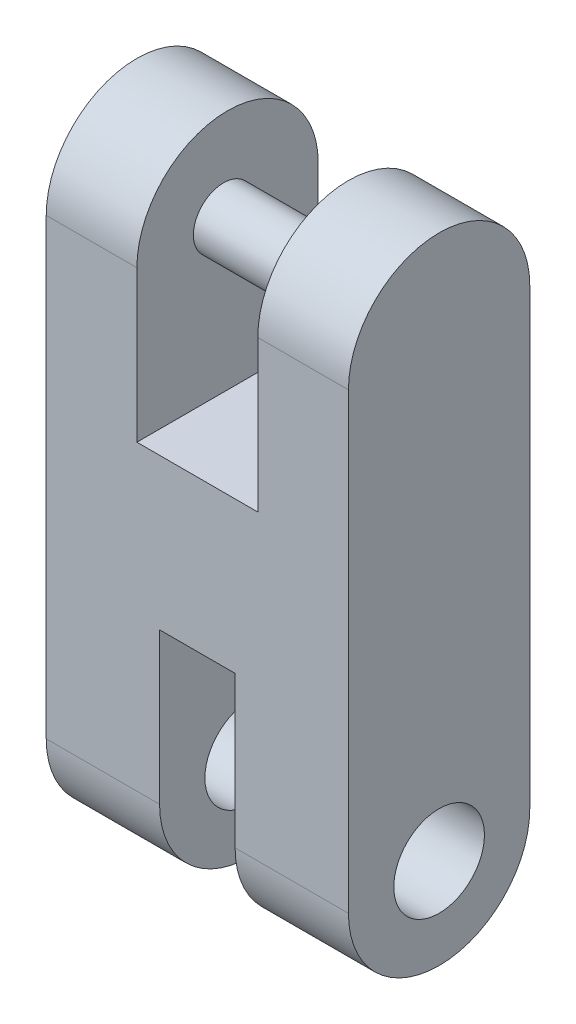
SolidWorks part; units mm, degrees
ref_plane "Alzado" through (0, 0, 0) normal (0, 0, 1) x (1, 0, 0)
ref_plane "Planta" through (0, 0, 0) normal (0, 1, 0) x (1, 0, 0)
ref_plane "Vista lateral" through (0, 0, 0) normal (1, 0, 0) x (0, 0, -1)
sketch "Croquis1" plane through (0, 0, 0) normal (0, 0, 1) x (1, 0, 0)
  line L0 (-7, 21) -> (-7, 13)
  line L1 (0, 0) -> (-3.75, 0)
  line L2 (0, 0) -> (0, 21)
  line L3 (0, 21) -> (-3, 21)
  line L4 (-10, 0) -> (-10, 21)
  line L5 (-7, 13) -> (-3, 13)
  line L6 (-3, 13) -> (-3, 21)
  line L7 (-6.25, 0) -> (-6.25, 8)
  line L8 (-6.25, 8) -> (-3.75, 8)
  line L9 (-3.75, 8) -> (-3.75, 0)
  line L10 (-7, 21) -> (-10, 21)
  line L11 (-6.25, 0) -> (-10, 0)
  line L12 (-10, 21) -> (-10, 24.8643) construction
  line L13 (-10, 24.8643) -> (0, 24.8643) construction
  line L14 (0, 24.8643) -> (0, 21) construction
  line L15 (-10, 0) -> (-10, -2.8007) construction
  line L16 (-10, -2.8007) -> (0, -2.8007) construction
  line L17 (0, -2.8007) -> (0, 0) construction
  line L18 (-5, 24.8643) -> (-5, -2.8007) construction
  dimension "D1" = 3
  dimension "D2" = 3
  dimension "D3" = 8
  dimension "D4" = 8
  dimension "D5" = 5
  dimension "D6" = 2.5
  dimension "D7" = 4
  dimension "D8" = 1.25
extrude "Saliente-Extruir1" add sketch "Croquis1" along normal blind 6
fillet "Redondeo1" 2 edges at (-1.875, 0, 6) (-1.875, 0, 0) type full round first side face at (-5, 10.5, 6) second side face at (-5, 10.5, 0) middle face at (-1.875, 0, 3)
fillet "Redondeo2" 2 edges at (-1.5, 21, 6) (-1.5, 21, 0) type full round first side face at (-5, 11, 6) second side face at (-5, 11, 0) middle face at (-1.5, 21, 3)
fillet "Redondeo3" 2 edges at (-8.5, 21, 0) (-8.5, 21, 6) type full round first side face at (-5, 10.5, 0) second side face at (-5, 10.5, 6) middle face at (-8.5, 21, 3)
fillet "Redondeo4" 2 edges at (-8.125, 0, 0) (-8.125, 0, 6) type full round first side face at (-5, 10, 0) second side face at (-5, 10, 6) middle face at (-8.125, 0, 3)
sketch "Croquis2" plane through (0, 0, 0) normal (1, 0, 0) x (0, 0, -1)
  line L0 (-3, 21) -> (-3, 0) construction
  line L1 (-6, 3) -> (0, 3) construction
  line L2 (-6, 18) -> (0, 18) construction
  circle A0 centre (-3, 3) radius 1.5
  arc A1 (0, 18) -> (-6, 18) centre (-3, 18) ccw construction
  arc A2 (-6, 3) -> (0, 3) centre (-3, 3) ccw construction
  dimension "D1" = 3
extrude "Cortar-Extruir1" cut sketch "Croquis2" against normal up to surface (10 mm away) up to face at (-10, 10.5, 3)
sketch "Croquis4" plane through (-7, 0, 0) normal (1, 0, 0) x (0, 0, -1)
  line L0 (-6, 18) -> (0, 18) construction
  line L1 (-3, 21) -> (-3, 18) construction
  arc A0 (0, 18) -> (-6, 18) centre (-3, 18) ccw construction
  circle A1 centre (-3.1309, 18) radius 1
  dimension "D1" = 2
extrude "Saliente-Extruir3" add sketch "Croquis4" along normal up to next
